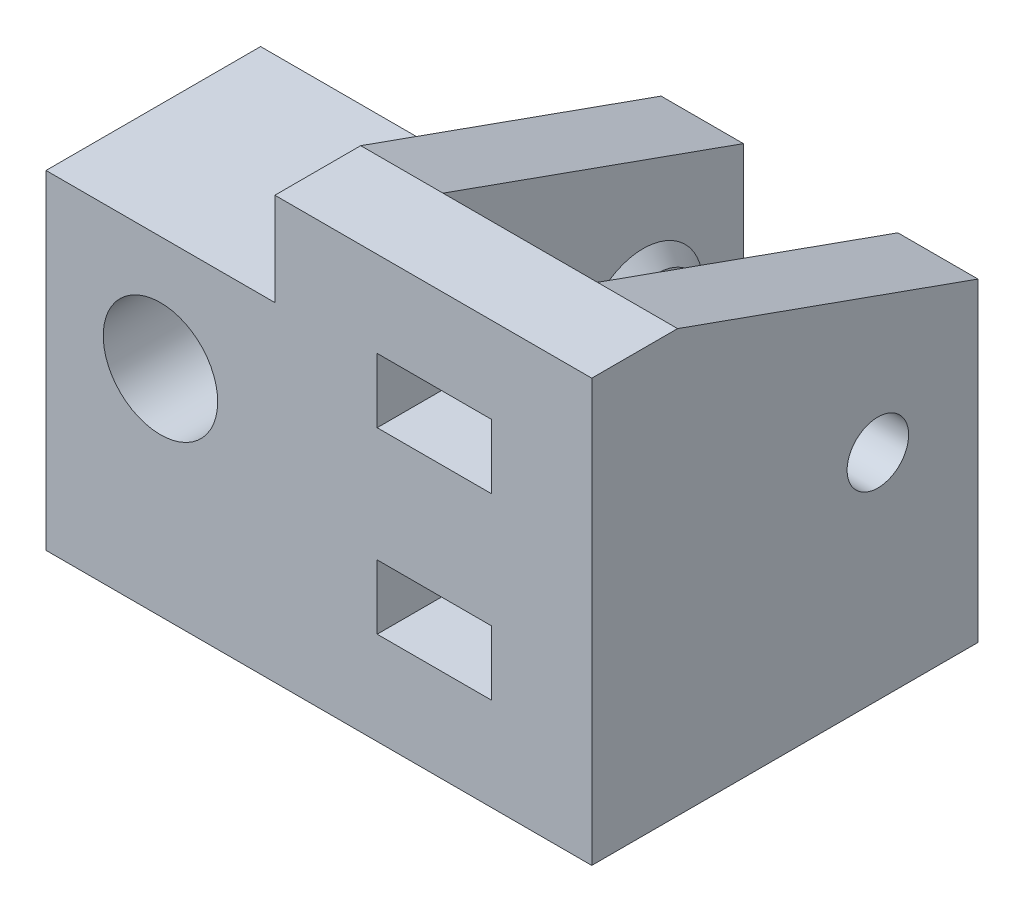
SolidWorks part; units mm, degrees
ref_plane "Alzado" through (0, 0, 0) normal (0, 0, 1) x (1, 0, 0)
ref_plane "Planta" through (0, 0, 0) normal (0, 1, 0) x (1, 0, 0)
ref_plane "Vista lateral" through (0, 0, 0) normal (1, 0, 0) x (0, 0, -1)
sketch "Croquis1" plane through (0, 0, 0) normal (0, 0, 1) x (1, 0, 0)
  line L1 (8, 8) -> (-8, 8)
  line L2 (8, 8) -> (8, -15)
  line L3 (8, -15) -> (-8, -15)
  line L4 (-8, 8) -> (-8, -15)
  circle A0 centre (0, 0) radius 4
  point P8 (0, 8)
  dimension "D1" = 8
  dimension "D2" = 16
  dimension "D3" = 8
  dimension "D4" = 15
extrude "Saliente-Extruir1" add sketch "Croquis1" along normal blind 10
sketch "Croquis2" plane through (0, 0, 0) normal (0, 0, -1) x (-1, 0, 0)
  line L4 (-8, 8) -> (-8, -15)
  line L5 (-8, -15) -> (8, -15)
  line L6 (8, -15) -> (8, 8)
  line L7 (8, 8) -> (-8, 8)
  line L8 (-8, 8) -> (-8, -15)
  line L9 (-8, -15) -> (8, -15)
  line L10 (8, -15) -> (8, 8)
  line L11 (8, 8) -> (-8, 8)
  dimension "D1" = 0
extrude "Saliente-Extruir2" add sketch "Croquis2" along normal blind 5
sketch "Croquis3" plane through (0, 0, 10) normal (0, 0, 1) x (1, 0, 0)
  line L0 (19.15, -4) -> (19.15, 4) construction
  line L1 (8, -15) -> (30.15, -15)
  line L2 (8, -15) -> (8, 14.5)
  line L3 (8, 14.5) -> (30.15, 14.5)
  line L4 (30.15, -15) -> (30.15, 14.5)
  line L5 (15.15, 4) -> (23.15, 4)
  line L6 (15.15, 4) -> (15.15, 8.5)
  line L7 (15.15, 8.5) -> (23.15, 8.5)
  line L8 (23.15, 4) -> (23.15, 8.5)
  line L9 (15.15, -4) -> (23.15, -4)
  line L10 (15.15, -4) -> (15.15, -8.5)
  line L11 (15.15, -8.5) -> (23.15, -8.5)
  line L12 (23.15, -4) -> (23.15, -8.5)
  line L13 (8, 8) -> (-8, 8) construction
  point P13 (19.15, 4)
  point P17 (19.15, 0)
  dimension "D1" = 8
  dimension "D2" = 8
  dimension "D3" = 19.15
  dimension "D4" = 4
  dimension "D5" = 11
  dimension "D6" = 8.5
  dimension "D7" = 6.5
extrude "Saliente-Extruir3" add sketch "Croquis3" against normal blind 6
sketch "Croquis4" plane through (30.15, 0, 0) normal (1, 0, 0) x (0, 0, -1)
  line L0 (-4, -15) -> (-4, 14.5) construction
  line L1 (-4, 14.5) -> (17, 7)
  line L2 (17, 7) -> (17, -15)
  line L3 (17, -15) -> (-4, -15)
  line L4 (-4, -15) -> (-4, 14.5)
  circle A0 centre (10, 0) radius 2.15
  dimension "D1" = 4.3
  dimension "D2" = 14
  dimension "D3" = 7
  dimension "D4" = 7
extrude "Saliente-Extruir4" add sketch "Croquis4" against normal blind 5.6
sketch "Croquis5" plane through (24.55, 0, 0) normal (-1, 0, 0) x (0, 0, 1)
  line L4 (4, -15) -> (4, 14.5)
  line L5 (4, 14.5) -> (-17, 7)
  line L6 (-17, 7) -> (-17, -15)
  line L7 (-17, -15) -> (4, -15)
  line L8 (4, -15) -> (4, 14.5)
  line L9 (4, 14.5) -> (-17, 7)
  line L10 (-17, 7) -> (-17, -15)
  line L11 (-17, -15) -> (4, -15)
  circle A0 centre (-10, 0) radius 2.15 construction
  circle A1 centre (-10, 0) radius 2.15
  dimension "D1" = 0
extrude "Saliente-Extruir5" add sketch "Croquis5" along normal up to surface (16.55 mm away) from offset 10.8 up to face at (8, -3.5, -0.5)
sketch "Croquis6" plane through (24.55, 0, 0) normal (-1, 0, 0) x (0, 0, 1)
  circle A0 centre (-10, 0) radius 2.15 construction
  circle A1 centre (-10, 0) radius 2.15
  circle A2 centre (-10, 0) radius 3.15
  dimension "D1" = 1
extrude "Saliente-Extruir6" add sketch "Croquis6" along normal blind 1
sketch "Croquis7" plane through (13.75, 0, 0) normal (1, 0, 0) x (0, 0, -1)
  circle A0 centre (10, 0) radius 2.15 construction
  circle A1 centre (10, 0) radius 3.15
  circle A2 centre (10, 0) radius 3.15
  circle A3 centre (10, 0) radius 2.15
  dimension "D1" = 0
extrude "Saliente-Extruir7" add sketch "Croquis7" along normal blind 1
chamfer "Chaflán1" distance 1 angle 45 2 edges at (13.75, 0, -6.85) (24.55, 0, -13.15)
sketch "Croquis8" plane through (0, -15, 0) normal (0, -1, 0) x (1, 0, 0)
  line L1 (24.55, 4) -> (13.75, 4)
  line L2 (24.55, 4) -> (24.55, -17)
  line L3 (24.55, -17) -> (13.75, -17)
  line L4 (13.75, 4) -> (13.75, -17)
extrude "Saliente-Extruir8" add sketch "Croquis8" against normal blind 3
